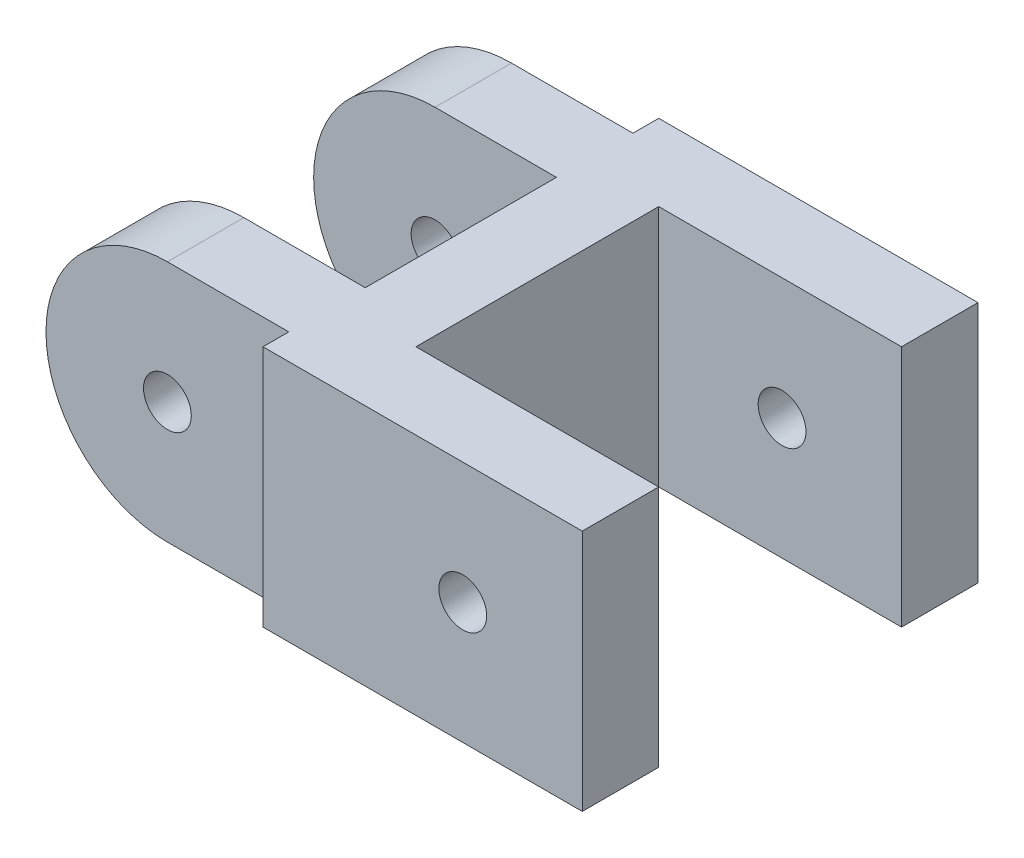
SolidWorks part; units mm, degrees
ref_plane "Front Plane" through (0, 0, 0) normal (0, 0, 1) x (1, 0, 0)
ref_plane "Top Plane" through (0, 0, 0) normal (0, 1, 0) x (1, 0, 0)
ref_plane "Right Plane" through (0, 0, 0) normal (1, 0, 0) x (0, 0, -1)
sketch "Sketch1" plane through (0, 0, 0) normal (0, 1, 0) x (1, 0, 0)
  line L0 (10.375, 18.45) -> (-15.025, 18.45)
  line L1 (-15.025, 18.45) -> (-15.025, -6.95)
  line L2 (-15.025, -6.95) -> (10.375, -6.95)
  line L3 (10.375, -6.95) -> (10.375, -14.95)
  line L4 (10.375, -14.95) -> (-23.025, -14.95)
  line L5 (-23.025, -14.95) -> (-23.025, -12.25)
  line L6 (-23.025, -12.25) -> (-48.425, -12.25)
  line L7 (-48.425, -12.25) -> (-48.425, -4.25)
  line L8 (-48.425, -4.25) -> (-23.025, -4.25)
  line L9 (-23.025, -4.25) -> (-23.025, 15.75)
  line L10 (-23.025, 15.75) -> (-48.425, 15.75)
  line L11 (-48.425, 15.75) -> (-48.425, 23.75)
  line L12 (-48.425, 23.75) -> (-23.025, 23.75)
  line L13 (-23.025, 23.75) -> (-23.025, 26.45)
  line L14 (-23.025, 26.45) -> (10.375, 26.45)
  line L15 (10.375, 26.45) -> (10.375, 18.45)
  dimension "D1" = 8
  dimension "D2" = 8
  dimension "D3" = 8
  dimension "D4" = 20
  dimension "D5" = 25.4
  dimension "D6" = 25.4
  dimension "D7" = 8
  dimension "D8" = 25.4
extrude "Boss-Extrude1" add sketch "Sketch1" along normal blind 25.4
fillet "Fillet1" radius 12.7 4 edges at (-48.425, 25.4, -19.75) (-48.425, 0, -19.75) (-48.425, 0, 8.25) (-48.425, 25.4, 8.25)
sketch "Sketch2" plane through (0, 0, 12.25) normal (0, 0, 1) x (1, 0, 0)
  circle A0 centre (-35.725, 12.7) radius 2.5
  dimension "D1" = 5
extrude "Cut-Extrude1" cut sketch "Sketch2" against normal up to surface (36 mm away) up to face at (-34.2371, 12.7, -23.75)
sketch "Sketch3" plane through (0, 0, 14.95) normal (0, 0, 1) x (1, 0, 0)
  line L0 (10.375, 25.4) -> (10.375, 0) construction
  circle A0 centre (-2.125, 12.7) radius 2.5
  dimension "D2" = 5
  dimension "D1" = 12.5
extrude "Cut-Extrude2" cut sketch "Sketch3" against normal up to surface (41.4 mm away) up to face at (-6.325, 12.7, -26.45)
